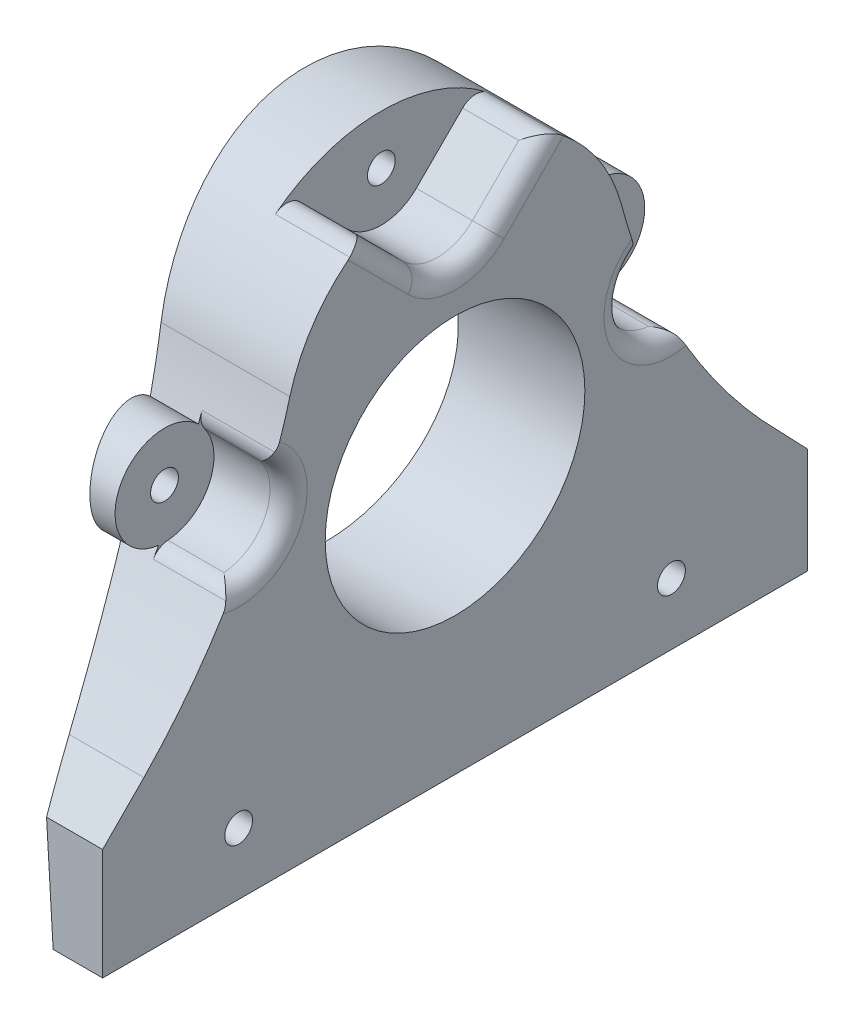
SolidWorks part; units mm, degrees
ref_plane "Plano frontal" through (0, 0, 0) normal (0, 0, 1) x (1, 0, 0)
ref_plane "Plano superior" through (0, 0, 0) normal (0, 1, 0) x (1, 0, 0)
ref_plane "Plano direito" through (0, 0, 0) normal (1, 0, 0) x (0, 0, -1)
sketch "Esboço1" plane through (0, 0, 0) normal (1, 0, 0) x (0, 0, -1)
  line L0 (0, 0) -> (-11.0135, 201.8152)
  line L1 (-18.5, 339) -> (-28.5149, 339)
  line L2 (-28.5149, 339) -> (-10.0149, 0)
  line L3 (-10.0149, 0) -> (0, 0)
  line L4 (123.9851, 0) -> (123.9851, 403.6304) construction
  line L5 (123.9851, 201.8152) -> (-21.0284, 201.8152)
  line L7 (-26.8409, 308.326) -> (-16.8261, 308.326)
  line L8 (123.9851, 211.8152) -> (123.9851, 201.8152)
  line L9 (123.9851, 211.8152) -> (-11.5592, 211.8152)
  line L10 (-11.5592, 211.8152) -> (-18.5, 339)
  line L11 (83.8614, 211.8152) -> (83.8614, 201.8152)
  line L12 (-10.0149, 0) -> (-319.8527, 0) construction
  dimension "D1" = 339
  dimension "D2" = 305
  dimension "D3" = 134
  dimension "D4" = 10
  dimension "D5" = 10
revolve "Revolução1" add sketch "Esboço1" angle 360 about L4 region at (0, 203.3514, 16.021)
sketch "Esboço5" plane through (0, 0, 0) normal (1, 0, 0) x (0, 0, -1)
  line L0 (0, 0) -> (0, 300.2576) construction
  line L1 (-21.0284, 201.8152) -> (268.9986, 201.8152) construction
  line L2 (123.9851, 201.8152) -> (123.9851, 308.326) construction
  line L3 (274.8112, 308.326) -> (-26.8409, 308.326) construction
  circle A0 centre (123.9851, 255.0706) radius 15.25
  dimension "D1" = 30.5
extrude "Corte-extrusão2" cut sketch "Esboço5" against normal through all and the other way through all
sketch "Esboço8" plane through (0, 0, 0) normal (0, 1, 0) x (1, 0, 0)
  line L1 (0, 123.9851) -> (-265.8618, 277.4805)
  line L2 (0, 123.9851) -> (-265.8618, -29.5103)
  line L3 (0, 123.9851) -> (-306.9908, 123.9851) construction
  circle A0 centre (0, 123.9851) radius 306.9908
  point P3 (0, 123.9851)
  dimension "D3" = 613.9816
  dimension "D1" = 60
  dimension "D2" = 30
extrude "Corte-extrusão5" cut sketch "Esboço8" along normal through all contours L2 A0 L1 region at (39.0873, 0, -123.9851)
sketch "Esboço9" plane through (0, 0, 0) normal (1, 0, 0) x (0, 0, -1)
  line L0 (56.2129, 211.8152) -> (191.7573, 211.8152)
  line L1 (91.9851, 255.0706) -> (91.9851, 211.8152)
  line L2 (155.9851, 255.0706) -> (155.9851, 211.8152)
  line L3 (91.9851, 255.0706) -> (66.9851, 255.0706)
  line L4 (66.9851, 255.0706) -> (66.9851, 211.8152)
  line L5 (155.9851, 255.0706) -> (180.9851, 255.0706)
  line L6 (180.9851, 255.0706) -> (180.9851, 211.8152)
  line L7 (79.4851, 255.0706) -> (79.4851, 240.0706) construction
  line L8 (123.9851, 211.8152) -> (123.9851, 173.8203) construction
  circle A0 centre (123.9851, 255.0706) radius 21
  arc A1 (155.9851, 255.0706) -> (91.9851, 255.0706) centre (123.9851, 255.0706) ccw
  circle A2 centre (79.4851, 240.0706) radius 2.25
  circle A3 centre (168.4851, 240.0706) radius 2.25
  circle A4 centre (123.9851, 255.0706) radius 15.25 construction
  point P0 (123.9851, 255.0706)
  dimension "D1" = 42
  dimension "D3" = 4.5
  dimension "D4" = 32
  dimension "D6" = 42
  dimension "D2" = 25
  dimension "D5" = 15
extrude "Ressalto-extrusão1" add sketch "Esboço9" against normal up to surface (2.9767 mm away) from offset 120 contours L6 L5 L2 L0 A3 | L2 A1 L1 L0 A0 | L3 L4 L0 L1 A2 | A2 | A3 region at (0, 233.344, -79.4851) region at (0, 233.4429, -92.973) region at (0, 233.344, -168.4851) region at (0, 240.0706, -79.4851) region at (0, 240.0706, -168.4851) up to face at (-138.3754, 268.0068, -115.9093) offset against normal yes
sketch "Esboço10" plane through (0, 211.8152, 0) normal (0, 1, 0) x (1, 0, 0)
  line L5 (-120, 180.9851) -> (-120, 66.9851)
  line L8 (-117.3849, 56.2129) -> (-34.7482, 103.9232)
  line L9 (-34.7482, 144.047) -> (-117.3849, 191.7573)
  line L13 (-117.3849, 56.2129) -> (-34.7482, 103.9232)
  line L14 (-34.7482, 144.047) -> (-117.3849, 191.7573)
  line L19 (-120, 180.9851) -> (-120, 66.9851)
  line L22 (-122.9767, 180.9851) -> (-120, 180.9851)
  line L25 (-122.9767, 180.9851) -> (-120, 180.9851)
  line L27 (-120, 66.9851) -> (-122.9767, 66.9851)
  line L28 (-120, 66.9851) -> (-122.9767, 66.9851)
  arc A3 (-117.3849, 191.7573) -> (-122.9767, 180.9851) centre (0, 123.9851) ccw
  arc A4 (-122.9767, 66.9851) -> (-117.3849, 56.2129) centre (0, 123.9851) ccw
  arc A5 (-34.7482, 144.047) -> (-34.7482, 103.9232) centre (0, 123.9851) ccw
  arc A6 (-117.3849, 191.7573) -> (-122.9767, 180.9851) centre (0, 123.9851) ccw
  arc A8 (-34.7482, 144.047) -> (-34.7482, 103.9232) centre (0, 123.9851) ccw
  arc A12 (-122.9767, 66.9851) -> (-117.3849, 56.2129) centre (0, 123.9851) ccw
  dimension "D1" = 0
extrude "Corte-extrusão6" cut sketch "Esboço10" against normal through all
sketch "Esboço11" plane through (-120, 0, 0) normal (1, 0, 0) x (0, 0, -1)
  line L0 (88.9851, 221.8152) -> (158.9851, 221.8152) construction
  line L1 (66.9851, 201.8152) -> (180.9851, 201.8152)
  line L2 (123.9851, 211.8152) -> (123.9851, 274.5303) construction
  line L3 (66.9851, 229.8152) -> (55.7218, 229.8152)
  line L4 (191.7573, 211.8152) -> (180.9851, 211.8152)
  line L5 (180.9851, 211.8152) -> (180.9851, 201.8152)
  line L6 (180.9851, 201.8152) -> (191.7573, 201.8152)
  line L7 (191.7573, 201.8152) -> (191.7573, 211.8152)
  line L8 (191.7573, 211.8152) -> (180.9851, 211.8152)
  line L9 (155.9851, 255.0706) -> (180.9851, 228.9176)
  line L10 (55.7218, 229.8152) -> (56.7218, 229.8152)
  line L11 (180.9851, 211.8152) -> (191.7573, 211.8152)
  line L12 (191.7573, 211.8152) -> (194.3907, 308.326)
  line L13 (194.3907, 308.326) -> (53.5795, 308.326)
  line L14 (53.5795, 308.326) -> (56.2129, 211.8152)
  line L15 (180.9851, 211.8152) -> (180.9851, 201.8152)
  line L16 (66.9851, 201.8152) -> (66.9851, 211.8152)
  line L17 (66.9851, 201.8152) -> (66.9851, 211.8152)
  line L20 (180.9851, 211.8152) -> (191.7573, 211.8152)
  line L21 (191.7573, 211.8152) -> (194.3907, 308.326)
  line L22 (194.3907, 308.326) -> (53.5795, 308.326)
  line L23 (53.5795, 308.326) -> (56.2129, 211.8152)
  line L28 (180.9851, 201.8152) -> (191.7573, 201.8152)
  line L29 (191.7573, 201.8152) -> (191.7573, 211.8152)
  line L30 (66.9851, 211.8152) -> (56.2129, 211.8152)
  line L31 (56.2129, 211.8152) -> (56.2129, 201.8152)
  line L32 (56.2129, 201.8152) -> (66.9851, 201.8152)
  line L33 (56.7218, 229.8152) -> (56.7218, 211.8152)
  line L34 (66.9851, 211.8152) -> (56.2129, 211.8152)
  line L35 (56.2129, 211.8152) -> (56.2129, 201.8152)
  line L36 (56.2129, 201.8152) -> (66.9851, 201.8152)
  line L38 (192.224, 228.9174) -> (191.2236, 228.9176)
  line L39 (191.2236, 228.9176) -> (190.7569, 211.8152)
  line L41 (190.7569, 211.8152) -> (191.7573, 211.8152)
  line L43 (56.7218, 211.8152) -> (56.2129, 211.8152)
  line L45 (180.9851, 228.9176) -> (180.9851, 211.8152)
  line L46 (180.9851, 211.8152) -> (66.9851, 211.8152)
  line L47 (91.9851, 255.0706) -> (66.9851, 229.8152)
  line L48 (56.2129, 211.8152) -> (66.9851, 211.8152)
  line L49 (56.2129, 211.8152) -> (66.9851, 211.8152)
  line L50 (155.9851, 255.0706) -> (180.9851, 255.0706)
  line L51 (155.9851, 255.0706) -> (180.9851, 255.0706)
  line L52 (180.9851, 255.0706) -> (180.9851, 211.8152)
  line L53 (180.9851, 255.0706) -> (180.9851, 211.8152)
  line L60 (66.9851, 211.8152) -> (66.9851, 255.0706)
  line L61 (66.9851, 211.8152) -> (66.9851, 255.0706)
  line L62 (66.9851, 255.0706) -> (91.9851, 255.0706)
  line L63 (66.9851, 255.0706) -> (91.9851, 255.0706)
  circle A4 centre (158.9851, 221.8152) radius 2.25
  circle A5 centre (88.9851, 221.8152) radius 2.25
  arc A9 (155.9851, 255.0706) -> (91.9851, 255.0706) centre (123.9851, 255.0706) ccw
  arc A10 (155.9851, 255.0706) -> (91.9851, 255.0706) centre (123.9851, 255.0706) ccw
  line M19 (180.9851, 201.8152) -> (180.9851, 255.0706)
  line M20 (180.9851, 255.0706) -> (155.9851, 255.0706)
  arc M21 (155.9851, 255.0706) -> (91.9851, 255.0706) centre (123.9851, 255.0706) ccw
  line M22 (91.9851, 255.0706) -> (66.9851, 255.0706)
  line M23 (66.9851, 255.0706) -> (66.9851, 201.8152)
  line M24 (66.9851, 201.8152) -> (180.9851, 201.8152)
  circle M26 centre (123.9851, 255.0706) radius 21
  dimension "D5" = 4.5
  dimension "D6" = 4.5
  dimension "D4" = 70
  dimension "D7" = 18
  dimension "D9" = 35
  dimension "D11" = 1
  dimension "D12" = 1
  dimension "D1" = 0
  dimension "D2" = 0
  dimension "D3" = 0
extrude "Corte-extrusão9" cut sketch "Esboço11" against normal through all contours L23 L49 L8 L21 L22 M23 M22 M21 M20 M19 | L35 L36 L49 M23 | L28 L29 L8 M19 | M23 M24 M19 | A5 | M26 | L34 L33 L3 L23 | L2 M26 | L39 L8 L21 | L47 M22 M23 | L9 M20 M19 | L34 L3 L33 M23 | A4 | A5 region at (-120, 206.8152, -123.9851) region at (-120, 206.8152, -61.599) region at (-120, 206.8152, -186.3712) region at (-120, 220.8152, -61.8535) region at (-120, 220.3664, -182.6922) region at (-120, 221.7918, -56.3313) region at (-120, 246.6522, -75.3185) region at (-120, 220.3664, -191.4904) region at (-120, 246.3529, -172.6518) region at (-120, 221.8152, -88.9851) region at (-120, 255.0706, -123.9851)
fillet "Filete1" radius 100 2 edges at (-132.2085, 255.0706, -155.9851) (-132.2085, 255.0706, -91.9851)
sketch "Esboço12" plane through (-120, 0, 0) normal (1, 0, 0) x (0, 0, -1)
  arc A0 (153.5307, 267.3612) -> (94.5558, 267.637) centre (123.9851, 255.0706) ccw construction
  arc A1 (153.5307, 267.3612) -> (94.5558, 267.637) centre (123.9851, 255.0706) ccw
  arc A2 (73.6582, 236.5565) -> (94.5558, 267.637) centre (2.589, 306.9069) ccw construction
  arc A3 (73.6582, 236.5565) -> (94.5558, 267.637) centre (2.589, 306.9069) ccw
  arc A4 (153.5307, 267.3612) -> (173.5744, 236.6701) centre (245.8607, 305.7693) ccw construction
  arc A5 (153.5307, 267.3612) -> (173.5744, 236.6701) centre (245.8607, 305.7693) ccw
  arc A6 (150.9476, 278.0368) -> (173.5744, 236.6701) centre (246.8951, 303.6466) ccw
  arc A7 (150.9476, 278.0368) -> (97.2677, 278.1074) centre (124.0982, 270.8703) ccw
  arc A8 (73.6582, 236.5565) -> (97.2677, 278.1074) centre (5.1894, 302.944) ccw
  point P14 (124.1348, 287.0703)
  point P15 (124.1348, 298.6597)
extrude "Ressalto-extrusão2" add sketch "Esboço12" against normal up to surface (25.6624 mm away) up to face at (-148.4614, 272.8006, -112.7313)
sketch "Esboço13" plane through (-120, 0, 0) normal (1, 0, 0) x (0, 0, -1)
  line L0 (89.0617, 263.772) -> (158.9086, 263.772) construction
  line L1 (123.9851, 263.772) -> (123.9851, 271.9128) construction
  circle A0 centre (123.9851, 255.0706) radius 21 construction
  circle A1 centre (123.9851, 255.0706) radius 21
  arc A2 (121.7362, 291.0003) -> (126.234, 291.0003) centre (123.9851, 255.0706) cw
  arc A3 (88.1078, 255.8291) -> (94.5402, 269.6017) centre (89.0617, 263.772) cw
  circle A6 centre (123.9851, 291.0706) radius 2.25
  arc A7 (73.6582, 236.5565) -> (97.2677, 278.1074) centre (5.1894, 302.944) ccw construction
  arc A8 (159.7703, 255.9911) -> (153.6258, 269.5494) centre (158.9086, 263.772) ccw
  arc A9 (88.1078, 255.8291) -> (94.5402, 269.6017) centre (5.1894, 302.944) ccw
  arc A10 (150.9476, 278.0368) -> (173.5744, 236.6701) centre (246.8951, 303.6466) ccw construction
  arc A11 (153.6258, 269.5494) -> (155.9457, 263.772) centre (246.8951, 303.6466) ccw
  arc A12 (153.6258, 269.5494) -> (159.7703, 255.9911) centre (246.8951, 303.6466) ccw
  arc M6 (173.5744, 236.6701) -> (150.9476, 278.0368) centre (246.8951, 303.6466) cw
  arc M8 (97.2677, 278.1074) -> (73.6582, 236.5565) centre (5.1894, 302.944) cw
  dimension "D1" = 36
  dimension "D2" = 8
  dimension "D3" = 7.8285
extrude "Ressalto-extrusão3" add sketch "Esboço13" against normal up to surface (5.5777 mm away) from offset 18 contours A8 M6 | A3 M8 region at (-120, 264.6149, -87.2569) region at (-120, 264.5824, -160.6968) up to face at (-140.5765, 241.0424, -125.0126) offset against normal yes
sketch "Esboço15" plane through (-120, 0, 0) normal (1, 0, 0) x (0, 0, -1)
  line L5 (66.9851, 211.8152) -> (180.9851, 211.8152)
  line L6 (180.9851, 211.8152) -> (180.9851, 228.9176)
  line L7 (180.9851, 228.9176) -> (173.5744, 236.6701)
  line L8 (73.6582, 236.5565) -> (66.9851, 229.8152)
  line L9 (66.9851, 229.8152) -> (66.9851, 211.8152)
  line L10 (66.9851, 211.8152) -> (180.9851, 211.8152)
  line L11 (180.9851, 211.8152) -> (180.9851, 228.9176)
  line L12 (180.9851, 228.9176) -> (173.5744, 236.6701)
  line L13 (73.6582, 236.5565) -> (66.9851, 229.8152)
  line L14 (66.9851, 229.8152) -> (66.9851, 211.8152)
  arc A3 (150.9476, 278.0368) -> (173.5744, 236.6701) centre (246.8951, 303.6466) ccw
  arc A4 (150.9476, 278.0368) -> (97.2677, 278.1074) centre (124.0982, 270.8703) ccw
  arc A5 (73.6582, 236.5565) -> (97.2677, 278.1074) centre (5.1894, 302.944) ccw
  arc A6 (150.9476, 278.0368) -> (173.5744, 236.6701) centre (246.8951, 303.6466) ccw
  arc A7 (150.9476, 278.0368) -> (97.2677, 278.1074) centre (124.0982, 270.8703) ccw
  arc A8 (73.6582, 236.5565) -> (97.2677, 278.1074) centre (5.1894, 302.944) ccw
  dimension "D1" = 0
extrude "Corte-extrusão11" cut sketch "Esboço15" against normal blind 5.93
sketch "Esboço16" plane through (-125.93, 0, 0) normal (1, 0, 0) x (0, 0, -1)
  line L0 (124.1348, 298.6597) -> (124.1348, 290.6597) construction
  line L1 (118.4779, 285.0028) -> (109.1707, 294.31)
  line L2 (129.7916, 285.0028) -> (139.0703, 294.2815)
  arc A0 (150.9476, 278.0368) -> (97.2677, 278.1074) centre (124.0982, 270.8703) ccw construction
  arc A1 (118.4779, 285.0028) -> (129.7916, 285.0028) centre (124.1348, 290.6597) ccw
  circle A2 centre (89.0617, 263.772) radius 8
  circle A3 centre (158.9086, 263.772) radius 7.8285
  arc A4 (139.0703, 294.2815) -> (109.1707, 294.31) centre (124.0982, 270.8703) ccw
  dimension "D1" = 8
  dimension "D2" = 45
  dimension "D3" = 45
extrude "Corte-extrusão12" cut sketch "Esboço16" against normal up to surface (12.07 mm away) contours A2 | A1 L2 A4 L1 | A3 up to face at (-138, 264.8722, -86.7061)
sketch "Esboço18" plane through (-125.93, 0, 0) normal (1, 0, 0) x (0, 0, -1)
  circle A0 centre (89.0617, 263.772) radius 2.25
  circle A1 centre (158.9086, 263.772) radius 2.25
  circle A2 centre (124.1348, 290.6597) radius 2.25
  dimension "D1" = 4.5
  dimension "D2" = 4.5
  dimension "D3" = 4.5
extrude "Corte-extrusão13" cut sketch "Esboço18" against normal through all
fillet "Filete3" radius 3 6 edges at (-131.965, 255.8291, -88.1078) (-131.965, 269.6017, -94.5402) (-131.965, 255.9911, -159.7703) (-131.965, 269.5494, -153.6258) (-131.965, 294.2815, -139.0703) (-131.965, 294.31, -109.1707)
fillet "Filete4" radius 3 5 edges at (-125.93, 260.3867, -96.3101) (-125.93, 260.5406, -151.7781) (-125.93, 288.7477, -133.5365) (-125.93, 288.7637, -114.717) (-125.93, 282.6597, -124.1348) tangent propagation no
